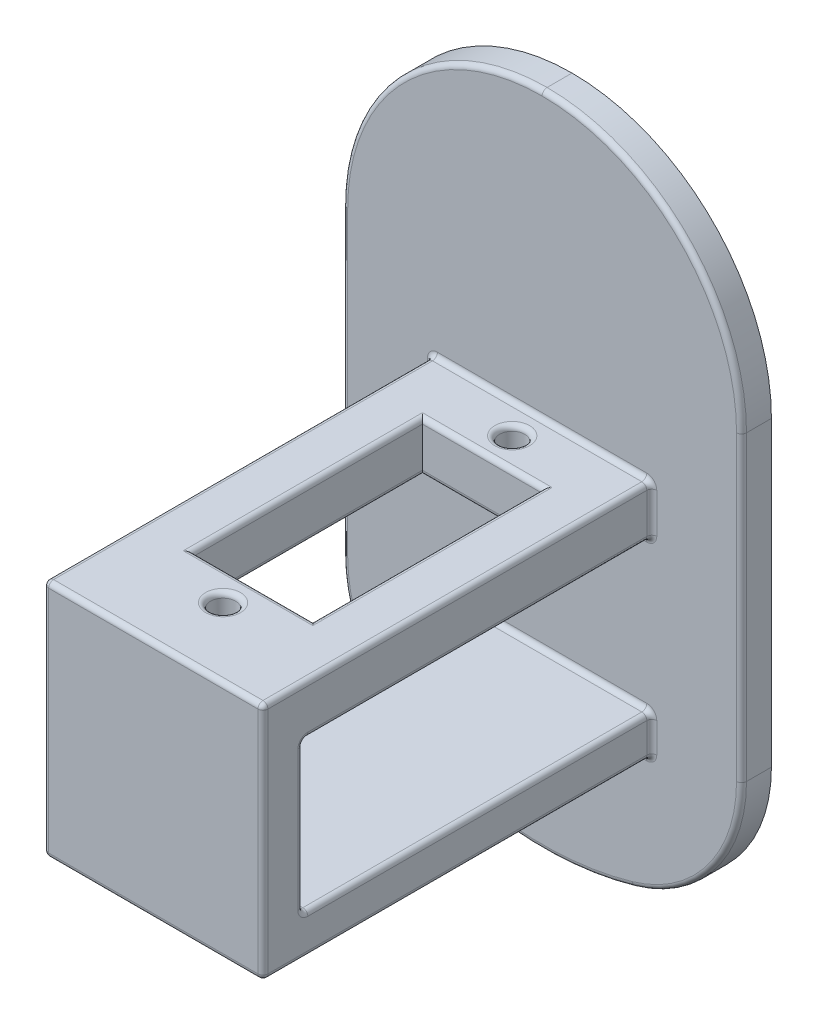
SolidWorks part; units mm, degrees
ref_plane "Front Plane" through (0, 0, 0) normal (0, 0, 1) x (1, 0, 0)
ref_plane "Top Plane" through (0, 0, 0) normal (0, 1, 0) x (1, 0, 0)
ref_plane "Right Plane" through (0, 0, 0) normal (1, 0, 0) x (0, 0, -1)
sketch "Sketch1" plane through (0, 0, 0) normal (0, 0, 1) x (1, 0, 0)
  circle A0 centre (0, 0) radius 33
  point P0 (0, 0)
  dimension "D1" = 66
extrude "Boss-Extrude1" add sketch "Sketch1" along normal blind 3
sketch "Sketch10" plane through (0, 0, 3) normal (0, 0, 1) x (1, 0, 0)
  line L0 (-20, 26.2488) -> (-20, -26.2488)
  line L1 (20, 26.2488) -> (20, -26.2488)
  circle A0 centre (0, 0) radius 33 construction
  arc A1 (-20, 26.2488) -> (-20, -26.2488) centre (0, 0) ccw
  arc A2 (20, -26.2488) -> (20, 26.2488) centre (0, 0) ccw
  dimension "D1" = 20
  dimension "D2" = 40
extrude "Cut-Extrude3" cut sketch "Sketch10" against normal blind 10
fillet "Fillet2" radius 20 2 edges at (-20, 26.2488, 1.5) (20, 26.2488, 1.5)
fillet "Fillet3" radius 15 2 edges at (20, -26.2488, 1.5) (-20, -26.2488, 1.5)
sketch "Sketch4" plane through (0, 0, 3) normal (0, 0, 1) x (1, 0, 0)
  line L1 (-11, 4.5) -> (11, 4.5)
  line L2 (-11, 4.5) -> (-11, -0.5)
  line L3 (-11, -0.5) -> (11, -0.5)
  line L4 (11, 4.5) -> (11, -0.5)
  line L5 (-11, 4.5) -> (11, -0.5) construction
  line L6 (-11, -0.5) -> (11, 4.5) construction
  point P0 (0, 2)
  dimension "D1" = 22
  dimension "D2" = 5
  dimension "D3" = 2
extrude "Boss-Extrude2" add sketch "Sketch4" along normal blind 35
sketch "Sketch5" plane through (0, 4.5, 0) normal (0, 1, 0) x (1, 0, 0)
  line L1 (-6, -9) -> (6, -9)
  line L2 (-6, -9) -> (-6, -32)
  line L3 (-6, -32) -> (6, -32)
  line L4 (6, -9) -> (6, -32)
  line L5 (-6, -9) -> (6, -32) construction
  line L6 (-6, -32) -> (6, -9) construction
  line L7 (-11, -38) -> (-11, -3) construction
  line L8 (11, -38) -> (-11, -38) construction
  point P0 (0, -20.5)
  point P10 (-11, -20.5)
  point P12 (0, -38)
  dimension "D1" = 12
  dimension "D2" = 23
extrude "Cut-Extrude1" cut sketch "Sketch5" against normal blind 5
sketch "Sketch6" plane through (0, 4.5, 0) normal (0, 1, 0) x (1, 0, 0)
  line L0 (0, -6) -> (0, -35) construction
  line L1 (-6, -9) -> (-6, -32) construction
  line L2 (-6, -32) -> (6, -32) construction
  circle A0 centre (0, -6) radius 1.25
  circle A1 centre (0, -35) radius 1.25
  point P4 (0, -20.5)
  point P7 (-6, -20.5)
  point P10 (0, -32)
  dimension "D1" = 2.5
  dimension "D2" = 29
extrude "Cut-Extrude2" cut sketch "Sketch6" against normal blind 5
sketch "Sketch7" plane through (0, 0, 38) normal (0, 0, 1) x (1, 0, 0)
  line L0 (11, -0.5) -> (11, 4.5) construction
  line L1 (-11, 4.5) -> (11, 4.5)
  line L2 (-11, 4.5) -> (-11, -15.5)
  line L3 (-11, -15.5) -> (11, -15.5)
  line L4 (11, 4.5) -> (11, -15.5)
  line L5 (11, -0.5) -> (11, 4.5) construction
  dimension "D1" = 20
extrude "Boss-Extrude3" add sketch "Sketch7" along normal blind 4
sketch "Sketch8" plane through (0, -15.5, 0) normal (0, -1, 0) x (1, 0, 0)
  line L1 (-11, 42) -> (11, 42)
  line L2 (-11, 42) -> (-11, 3)
  line L3 (-11, 3) -> (11, 3)
  line L4 (11, 42) -> (11, 3)
extrude "Boss-Extrude4" add sketch "Sketch8" along normal blind 4
sketch "Sketch9" plane through (0, -19.5, 0) normal (0, -1, 0) x (1, 0, 0)
  line L0 (-11, 3) -> (11, 3) construction
  circle A0 centre (0, 25.5) radius 3.75
  dimension "D1" = 7.5
  dimension "D2" = 22.5
extrude "Boss-Extrude5" add sketch "Sketch9" along normal blind 7
fillet "Fillet4" radius 0.5 45 edges at (11, -8, 38) (-11, -8, 38) (0, -26.5, 21.75) (11, -19.5, 22.5) (-11, -19.5, 22.5) (0, -19.5, 21.75) (-11, -0.5, 20.5) (0, -0.5, 38) (11, -0.5, 20.5) (-6, -0.5, 20.5) (0, -0.5, 9) (6, -0.5, 20.5) (0, -0.5, 32) (0, -0.5, 36.25) (0, -0.5, 7.25) (11, -15.5, 20.5) (0, -15.5, 38) (-11, -15.5, 20.5) (11, -7.5, 42) (0, -19.5, 42) (-11, -7.5, 42) (11, 4.5, 22.5) (0, 4.5, 42) (-11, 4.5, 22.5) (-6, 4.5, 20.5) (0, 4.5, 32) (6, 4.5, 20.5) (0, 4.5, 9) (0, 4.5, 36.25) (0, 4.5, 7.25) (-11, 2, 3) (0, -0.5, 3) (11, 2, 3) (0, 4.5, 3) (-16.9896, -26.3055, 3) (-20, -2.1458, 3) (-14.1421, 27.1421, 3) (14.1421, 27.1421, 3) (20, -2.1458, 3) (16.9896, -26.3055, 3) (0, -33, 3) (11, -17.5, 3) (0, -15.5, 3) (-11, -17.5, 3) (0, -19.5, 3)
